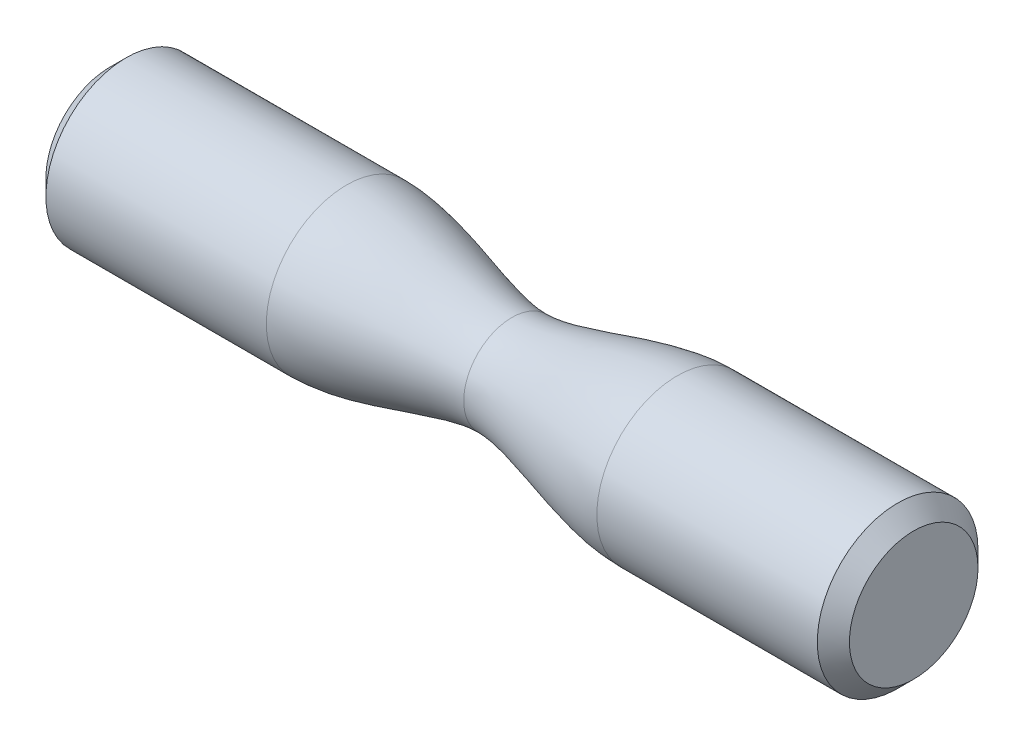
SolidWorks part; units mm, degrees
material "Alloy Steel"
ref_plane "Front" through (0, 0, 0) normal (0, 0, 1) x (1, 0, 0)
ref_plane "Top" through (0, 0, 0) normal (0, 1, 0) x (1, 0, 0)
ref_plane "Right" through (0, 0, 0) normal (1, 0, 0) x (0, 0, -1)
sketch "Sketch1" plane through (0, 0, 0) normal (0, 0, 1) x (1, 0, 0)
  line L0 (-7.9375, 0) -> (7.9375, 0) construction
  line L1 (7.9375, 1.5875) -> (7.9375, -1.5875) construction
  line L2 (-7.9375, 1.5875) -> (-7.9375, -1.5875) construction
  dimension "Length" = 15.875
  dimension "Diameter" = 3.175
sketch "Sketch2" plane through (0, 0, 0) normal (1, 0, 0) x (0, 0, -1)
  circle A0 centre (0, 0) radius 1.5875
extrude "Extrude1" add sketch "Sketch2" against normal up to vertex (7.9375 mm away) and the other way up to vertex (7.9375 mm away) up to point (-7.9375, 1.5875, 0) other way up to point (7.9375, 1.5875, 0)
chamfer "Chamfer1" distance 0.3175 angle 45 2 edges at (7.9375, 0, -1.5875) (-7.9375, 0, -1.5875)
sketch "Sketch3" plane through (0, 0, 0) normal (0, 0, 1) x (1, 0, 0)
  line L0 (0, 1.5875) -> (0, -1.5875) construction
  line L1 (7.62, 1.5875) -> (-7.62, 1.5875) construction
  line L2 (-7.62, -1.5875) -> (7.62, -1.5875) construction
  line L3 (7.9375, 0) -> (-7.9375, 0) construction
  line L4 (7.9375, -1.27) -> (7.9375, 1.27) construction
  line L5 (-7.9375, 1.27) -> (-7.9375, -1.27) construction
  line L6 (1.7736, 1.5875) -> (4.8523, 1.5875) construction
  line L7 (-0.4426, 0.9525) -> (0.4426, 0.9525) construction
  line L8 (3.2651, 1.5875) -> (-3.2651, 1.5875)
  spline S0 degree 3 poles (3.2651, 1.5875) (2.1144, 1.5875) (0.8785, 0.9525) (0, 0.9525) knots 0 0 0 0 1 1 1 1
  spline S1 degree 3 poles (-3.2651, 1.5875) (-2.1144, 1.5875) (-0.8785, 0.9525) (0, 0.9525) knots 0 0 0 0 1 1 1 1
  dimension "D1" = 0.635
revolve "Cut-Revolve1" cut sketch "Sketch3" angle 360 about L3 region at (0, 1.3577, 0)
equation "\"D1@Chamfer1\" = \"Diameter@Sketch1\"*.1"
